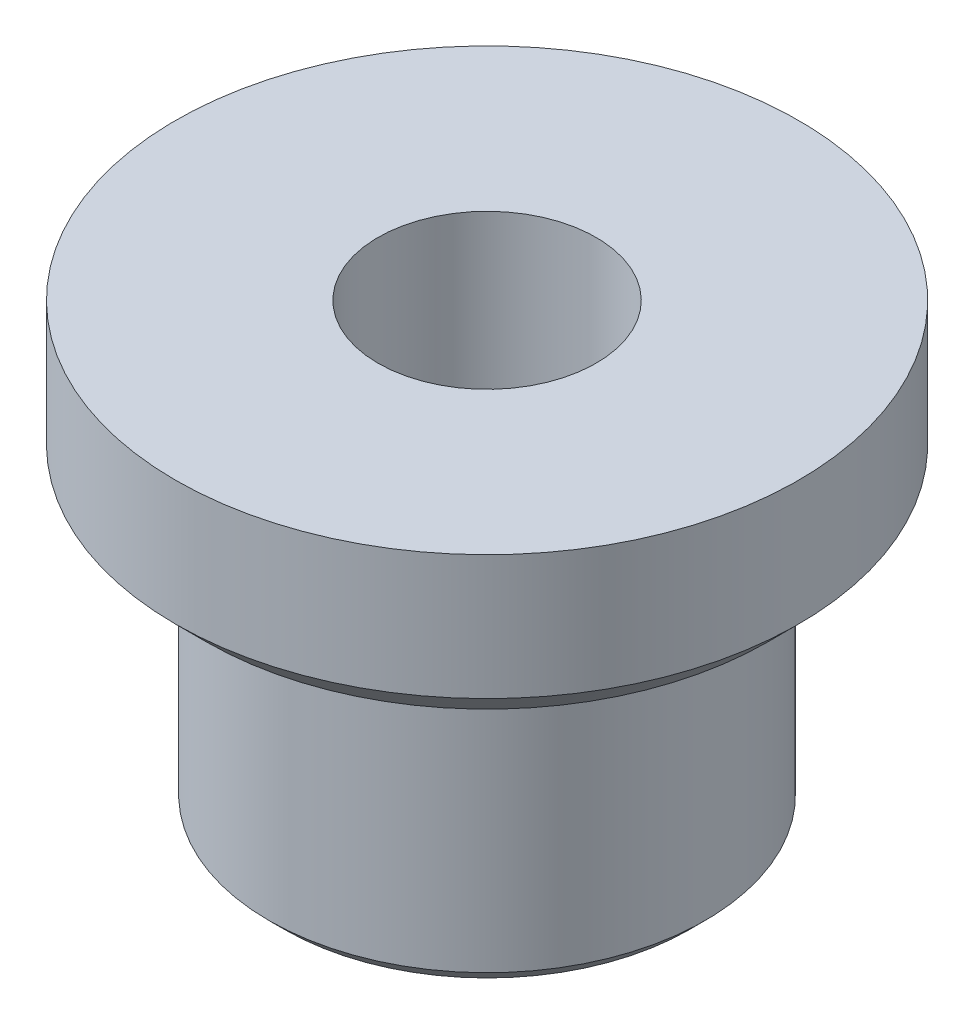
SolidWorks part; units mm, degrees
ref_plane "Front Plane" through (0, 0, 0) normal (0, 0, 1) x (1, 0, 0)
ref_plane "Top Plane" through (0, 0, 0) normal (0, 1, 0) x (1, 0, 0)
ref_plane "Right Plane" through (0, 0, 0) normal (1, 0, 0) x (0, 0, -1)
sketch "Sketch1" plane through (0, 0, 0) normal (0, 1, 0) x (1, 0, 0)
  line L1 (-10, 10) -> (10, 10)
  line L2 (-10, 10) -> (-10, -10)
  line L3 (-10, -10) -> (10, -10)
  line L4 (10, 10) -> (10, -10)
  line L5 (-10, 10) -> (10, -10) construction
  line L6 (-10, -10) -> (10, 10) construction
  line L7 (-7, 7) -> (7, 7)
  line L8 (-7, 7) -> (-7, -7)
  line L9 (-7, -7) -> (7, -7)
  line L10 (7, 7) -> (7, -7)
  line L11 (-7, 7) -> (7, -7) construction
  line L12 (-7, -7) -> (7, 7) construction
  line L13 (-5, 5) -> (5, 5)
  line L14 (-5, 5) -> (-5, -5)
  line L15 (-5, -5) -> (5, -5)
  line L16 (5, 5) -> (5, -5)
  line L17 (-5, 5) -> (5, -5) construction
  line L18 (-5, -5) -> (5, 5) construction
  circle A0 centre (0, 0) radius 1.65 construction
  circle A1 centre (0, 0) radius 3.3 construction
  point P0 (0, 0)
  point P6 (0, 0)
  dimension "D3" = 3.3
  dimension "D4" = 6.6
  dimension "D1" = 20
  dimension "D2" = 14
  dimension "D5" = 10
sketch "Sketch2" plane through (0, 0, 0) normal (0, 1, 0) x (1, 0, 0)
  circle A0 centre (0, 0) radius 1.65 construction
  circle A1 centre (0, 0) radius 3.3 construction
  circle A2 centre (0, 0) radius 1.65
  circle A3 centre (0, 0) radius 3.3
  point P0 (0, 0)
sketch "Sketch3" plane through (0, 0, 0) normal (0, 1, 0) x (1, 0, 0)
  circle A0 centre (0, 0) radius 7
  circle A1 centre (0, 0) radius 10
  dimension "D1" = 20
  dimension "D2" = 14
extrude "Base" add sketch "Sketch3" against normal blind 5 separate body
sketch "Sketch4" plane through (0, 0, 0) normal (0, 1, 0) x (1, 0, 0)
  circle A0 centre (0, 0) radius 5
  circle A2 centre (0, 0) radius 3.3
  circle A3 centre (0, 0) radius 1.65
  dimension "D1" = 10
  dimension "D2" = 6.6
  dimension "D3" = 3.3
extrude "Boss-Extrude4" add sketch "Sketch3<2>" against normal blind 14.24 contours A0 region at (0, 0, 0)
sketch "Sketch3<2>" plane through (0, 0, 0) normal (0, 1, 0) x (1, 0, 0) same geometry as "Sketch3"
extrude "Cut-Extrude4" cut sketch "Sketch4" against normal blind 5 contours A2 A3 region at (-3.2067, 0, 0)
extrude "Cut-Extrude5" cut sketch "Sketch4<3>" along normal blind 4.25 from surface contours A0 A2 | A3 | A2 A3 region at (-4.8586, 0, 0) region at (-3.2067, 0, 0) region at (0, 0, 0) starting at face at (0, -14.24, 7)
sketch "Sketch4<3>" plane through (0, 0, 0) normal (0, 1, 0) x (1, 0, 0) same geometry as "Sketch4"
extrude "Cut-Extrude6" cut sketch "Sketch4<4>" against normal through all contours A3 region at (0, 0, 0)
sketch "Sketch4<4>" plane through (0, 0, 0) normal (0, 1, 0) x (1, 0, 0) same geometry as "Sketch4"
other ".2 Move Face1" flip direction yes face at (0, -9.99, 5) face at (0, -5, 1.65) face at (0, -5, 1.65) face at (0, -5, 3.3) offset 0.2 parameters "D1"=0.2
chamfer "Chamfer1" distance 0.5 angle 45 2 edges at (0, -14.24, 5.2) (0, -14.24, 7)
chamfer "Chamfer2" distance 1 angle 45 1 edges at (0, -5, 10)
equation "\"D1@Boss-Extrude4\"=10 + 5 - 0.76"
